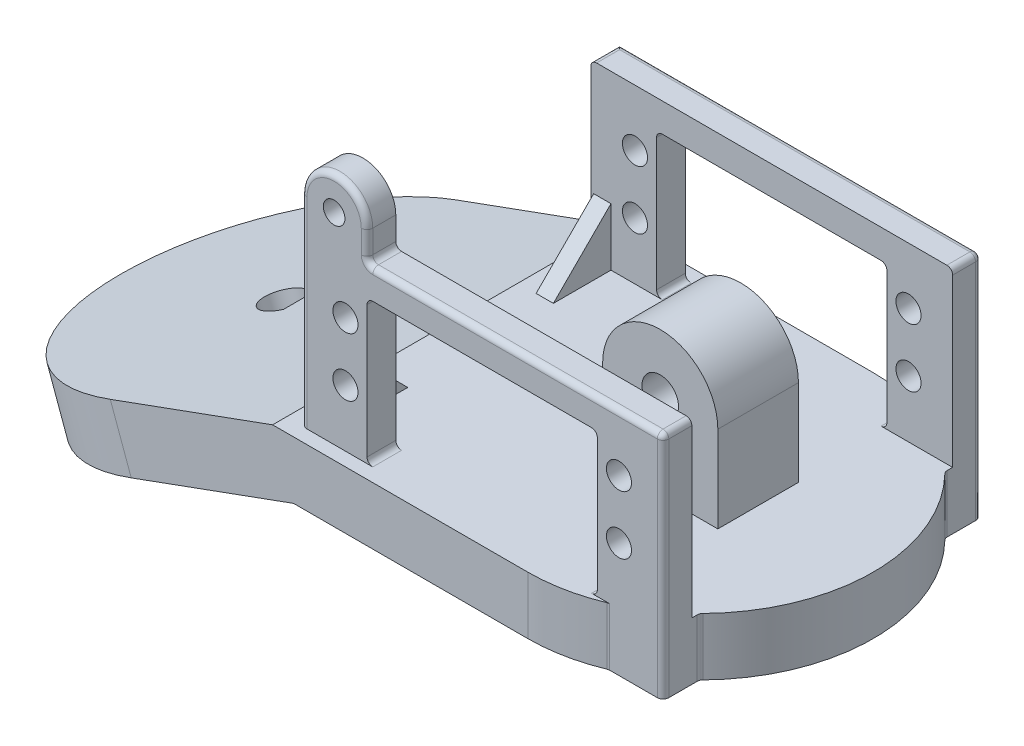
SolidWorks part; units mm, degrees
ref_plane "Plan de face" through (0, 0, 0) normal (0, 0, 1) x (1, 0, 0)
ref_plane "Plan de dessus" through (0, 0, 0) normal (0, 1, 0) x (1, 0, 0)
ref_plane "Plan de droite" through (0, 0, 0) normal (1, 0, 0) x (0, 0, -1)
sketch "Esquisse5" plane through (0, 0, 0) normal (0, 1, 0) x (1, 0, 0)
  line L0 (42.5, 0) -> (-42.5, 0) construction
  line L1 (42.5, -30) -> (-42.5, -30)
  line L2 (42.5, 30) -> (-42.5, 30)
  arc A0 (42.5, -30) -> (42.5, 30) centre (42.5, 0) ccw
  arc A1 (-42.5, 30) -> (-42.5, -30) centre (-42.5, 0) ccw
  point P2 (0, 0)
  dimension "D2" = 30
  dimension "D1" = 85
extrude "Boss.-Extru.3" add sketch "Esquisse5" along normal mid plane 10
sketch "Esquisse36" plane through (0, 0, 0) normal (0, 0, 1) x (1, 0, 0)
  line L0 (0, 0) -> (9.0993, -25)
  line L1 (9.0993, -25) -> (-112.5, -25)
  line L2 (-112.5, -25) -> (-112.5, 35)
  line L3 (-112.5, 35) -> (-12.739, 35)
  line L4 (-12.739, 35) -> (0, 0)
  line L5 (42.5, -5) -> (-42.5, -5) construction
  line L6 (42.5, 5) -> (-42.5, 5) construction
  line L7 (-42.5, 5) -> (-42.5, -5) construction
  dimension "D1" = 180
  dimension "D2" = 20
  dimension "D3" = 70
  dimension "D4" = 30
  dimension "D5" = 70
sketch "Esquisse7" plane through (0, 0, 0) normal (0, 0, 1) x (1, 0, 0)
  line L0 (42.5, 5) -> (32.5, 5)
  line L1 (-42.5, 5) -> (42.5, 5) construction
  line L2 (32.5, 5) -> (32.5, 20)
  line L3 (32.5, 20) -> (52.5, 20)
  line L4 (52.5, 20) -> (52.5, 5)
  line L5 (72.5, 5) -> (42.5, 5) construction
  line L6 (52.5, 5) -> (42.5, 5)
  arc A0 (32.5, 20) -> (52.5, 20) centre (42.5, 20) cw
  circle A1 centre (42.5, 20) radius 3.175
  dimension "D1" = 10
  dimension "D3" = 6.35
  dimension "D2" = 15
extrude "Boss.-Extru.5" add sketch "Esquisse7" along normal mid plane 14 contours A1 L3 A0 | A1 L3 L2 L0 L6 L4 region at (42.5, 12.1572, 0) region at (42.5, 24.5689, 0)
sketch "Esquisse10" plane through (0, -5, 0) normal (0, -1, 0) x (1, 0, 0)
  point P0 (42.5, 0)
ref_plane "Plan1" through (0, 0, 22.64) normal (0, 0, 1) x (1, 0, 0)
sketch "Esquisse13" plane through (0, 0, 22.64) normal (0, 0, 1) x (1, 0, 0)
  line L0 (-42.5, 5) -> (42.5, 5) construction
  line L1 (5.8, 5) -> (58.63, 5)
  line L2 (5.8, 5) -> (5.8, 29.91) construction
  line L3 (5.8, 29.91) -> (58.63, 29.91) construction
  line L4 (58.63, 5) -> (58.63, 29.91) construction
  line L5 (5.8, 5) -> (0.8, 5)
  line L6 (0.8, 5) -> (0.8, 34.91)
  line L7 (0.8, 34.91) -> (63.63, 34.91)
  line L8 (63.63, 34.91) -> (63.63, 5)
  line L9 (63.63, 5) -> (58.63, 5)
  line L10 (63.63, 5) -> (58.63, 5)
  line L11 (0.8, 5) -> (5.8, 5)
  line L12 (12.215, 5) -> (12.215, 29.91)
  line L13 (12.215, 29.91) -> (52.215, 29.91)
  line L14 (52.215, 29.91) -> (52.215, 5)
  line L15 (52.215, 5) -> (12.215, 5)
  circle A0 centre (42.5, 20) radius 3.175 construction
  circle A2 centre (55.97, 25.08) radius 2.18
  circle A3 centre (55.97, 14.92) radius 2.18
  circle A4 centre (8.47, 25.08) radius 2.18
  circle A5 centre (8.47, 14.92) radius 2.18
  point P6 (58.63, 17.455)
  point P24 (32.215, 29.91)
  point P26 (32.215, 34.91)
  dimension "D4" = 5
  dimension "D7" = 4.36
  dimension "D8" = 47.5
  dimension "D12" = 10.16
  dimension "D1" = 52.83
  dimension "D2" = 16.13
  dimension "D3" = 24.91
  dimension "D5" = 4.83
  dimension "D6" = 2.67
  dimension "D9" = 47.5
  dimension "D10" = 0
  dimension "D11" = 0
  dimension "D13" = 0
  dimension "D14" = 5
  dimension "D15" = 5
  dimension "D16" = 40
  dimension "D17" = 0
  dimension "D18" = 0
extrude "Boss.-Extru.8" add sketch "Esquisse13" along normal blind 5 contours L13 L14 L1 L9 L8 L7 L6 L5 L12 A5 A4 A3 A2 region at (3.3, 5.6959, 22.64)
ref_plane "Plan12" through (2.8, 0, 0) normal (-1, 0, 0) x (0, 0, 1)
mirror "Symétrie2" about plane through (0, 0, 0) normal (0, 0, 1) of "Boss.-Extru.8"
sketch "Esquisse14" plane through (0, 0, 0) normal (0, 0, 1) x (1, 0, 0)
  point P0 (42.5, 20)
sketch "Esquisse33" plane through (0, 5, 0) normal (0, -1, 0) x (1, 0, 0)
  line L0 (54.1632, -27.64) -> (63.63, -27.64) construction
  line L1 (63.63, 27.64) -> (54.1632, 27.64)
  line L2 (63.63, 27.64) -> (63.63, -27.64)
  line L3 (63.63, -27.64) -> (54.1632, -27.64)
  line L4 (54.1632, 27.64) -> (54.1632, -27.64)
  dimension "D1" = 0
  dimension "D2" = 0
extrude "Boss.-Extru.10" add sketch "Esquisse33" along normal up to surface (10 mm away) up to face at (0, -5, 0)
sketch "Esquisse34" plane through (0, 0, 0) normal (0, 1, 0) x (1, 0, 0)
  line L0 (0, 0) -> (0, 29.4868) construction
extrude "Enlèv. mat.-Extru.6" cut sketch "Esquisse36" against normal mid plane 130
ref_plane "Plan11" through (0, 0, 0) normal (-0.342, 0.9397, 0) x (0, 0, -1)
sketch "Esquisse35" plane through (0, 0, 0) normal (-0.342, 0.9397, 0) x (0, 0, -1)
  circle A0 centre (0, 30) radius 30
  dimension "D1" = 60
  dimension "D2" = 0
extrude "Boss.-Extru.11" add sketch "Esquisse35" along normal mid plane 10.64
sketch "Esquisse37" plane through (0, 0, 0) normal (0, 0, 1) x (1, 0, 0)
sketch "Esquisse38" plane through (-1.8195, 4.9992, 0) normal (-0.342, 0.9397, 0) x (0.9397, 0.342, 0)
  point P0 (0, 0)
  point P1 (-30, 0)
sketch "Esquisse39" plane through (1.8195, -4.9992, 0) normal (0.342, -0.9397, 0) x (0.9397, 0.342, 0)
  point P0 (-30, 0)
sketch "Esquisse40" plane through (0, 0, 0) normal (0, 0, 1) x (1, 0, 0)
  line L0 (-26.3712, -15.2598) -> (-30.0103, -5.2614)
  line L1 (-26.3712, -15.2598) -> (1.8195, -4.9992)
  line L2 (-30.0103, -5.2614) -> (-1.8195, 4.9992)
  line L3 (1.8195, -4.9992) -> (-1.8195, 4.9992)
  dimension "D1" = 0
extrude "Boss.-Extru.12" add sketch "Esquisse40" along normal mid plane 60
sketch "Esquisse41" plane through (-1.8195, 4.9992, 0) normal (-0.342, 0.9397, 0) x (0.9397, 0.342, 0)
  line L0 (-27.46, -2.2602) -> (-27.46, 2.2602)
  line L1 (0, -30) -> (0, 30) construction
  arc A1 (-27.46, -2.2602) -> (-27.46, 2.2602) centre (-30, 0) cw
  point P0 (0, 0)
  point P4 (-33.4, 0)
  dimension "D2" = 3.4
  dimension "D3" = 5.94
extrude "Enlèv. mat.-Extru.7" cut sketch "Esquisse41" against normal blind 60
sketch "Esquisse42" plane through (0, 0, 27.64) normal (0, 0, 1) x (1, 0, 0)
  line L0 (0.8, 34.91) -> (0.8, 39.91)
  line L1 (0.8, 39.91) -> (12.215, 39.91)
  line L2 (12.215, 39.91) -> (12.215, 34.91)
  line L3 (0.8, 34.91) -> (63.63, 34.91) construction
  line L4 (12.215, 34.91) -> (0.8, 34.91)
  line L5 (12.215, 5) -> (12.215, 29.91) construction
  arc A0 (0.8, 39.91) -> (12.215, 39.91) centre (6.5075, 39.91) cw
  circle A1 centre (6.5075, 39.91) radius 1.875
  line M15 (63.63, 34.91) -> (0.8, 34.91)
  dimension "D3" = 3.75
  dimension "D1" = 5
  dimension "D2" = 0
extrude "Boss.-Extru.13" add sketch "Esquisse42" against normal up to surface (5 mm away) contours A1 L1 A0 | A1 L1 L0 L2 M15 region at (6.5075, 37.2274, 27.64) region at (6.5075, 42.5291, 27.64) up to face at (10.65, 14.92, 22.64)
sketch "Esquisse45" plane through (2.8, 0, 0) normal (-1, 0, 0) x (0, 0, 1)
  line L0 (22.64, 14.9996) -> (12.64, 4.9996)
  line L1 (22.64, 5) -> (22.64, 39.91) construction
  line L2 (30, 4.9996) -> (-30, 4.9996) construction
  dimension "D1" = 10
  dimension "D2" = 10
rib "Nervure4" sketch "Esquisse45" sketch "Esquisse45" thickness 3 extrusion direction parallel to sketch draft on no parameters "D1"=3
fillet "Congé1" radius 1 6 edges at (54.1632, 0, 27.64) (63.63, 14.955, 27.64) (63.63, 0, 21.2961) (54.1632, 0, -27.64) (63.63, 0, -21.2961) (63.63, 14.955, -27.64)
mirror "Symétrie3" about plane through (0, 0, 0) normal (0, 0, 1) of "Nervure4"
fillet "Congé2" radius 1 19 edges at (0.8, 22.455, 27.64) (6.5075, 45.6175, 27.64) (12.215, 37.41, 27.64) (31.715, 34.91, -27.64) (63.3371, 34.91, -27.3471) (37.4225, 34.91, 27.64) (63.3371, 34.91, 27.3471) (63.63, 34.91, -24.64) (0.8, 34.91, -25.14) (52.215, 5, -25.14) (52.215, 29.91, -25.14) (12.215, 29.91, -25.14) (12.215, 5, -25.14) (12.215, 5, 25.14) (52.215, 5, 25.14) (52.215, 29.91, 25.14) (12.215, 29.91, 25.14) (12.215, 34.91, 25.14) (63.63, 34.91, 24.64)
